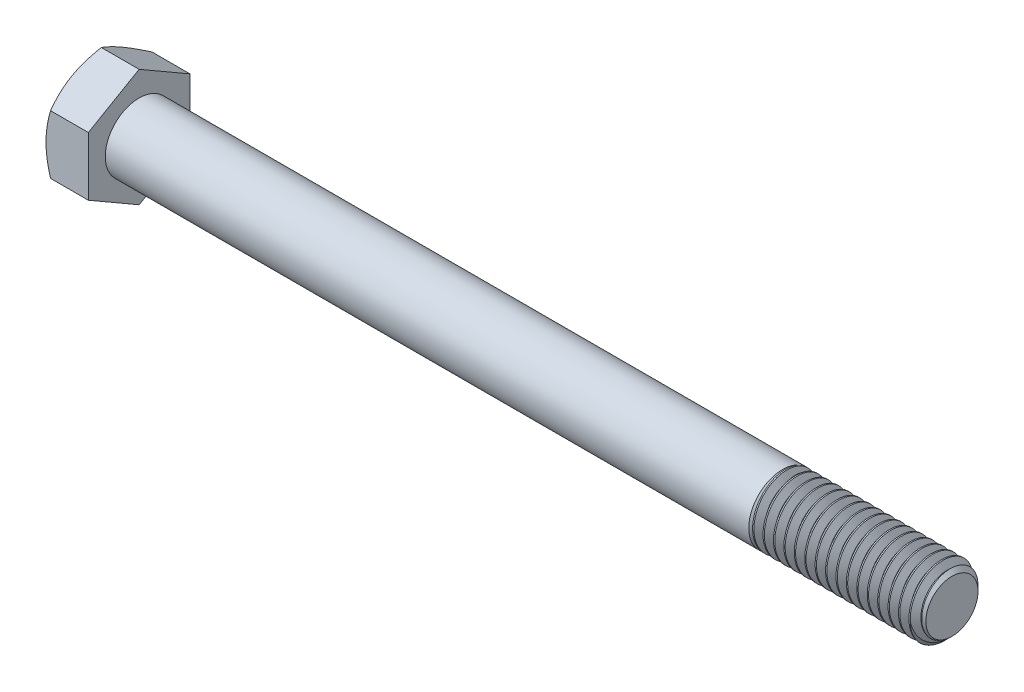
SolidWorks part; units mm, degrees
material "Plain Carbon Steel"
ref_plane "Front Plane" through (0, 0, 0) normal (0, 0, 1) x (1, 0, 0)
ref_plane "Top Plane" through (0, 0, 0) normal (0, 1, 0) x (1, 0, 0)
ref_plane "Right Plane" through (0, 0, 0) normal (1, 0, 0) x (0, 0, -1)
sketch "Sketch1" plane through (0, 0, 0) normal (0, 0, 1) x (1, 0, 0)
  line L0 (-80.1688, 0) -> (80.1688, 0) construction
  line L1 (80.1688, 6.35) -> (80.1688, -6.35) construction
  line L2 (-72.2313, 9.525) -> (-72.2313, -9.525) construction
  line L3 (-80.1688, 9.525) -> (-80.1688, -9.525) construction
  point P9 (-72.2313, 0)
  point P10 (73.3303, -6.35)
  dimension "Screw Dia" = 12.7
  dimension "Hex" = 19.05
  dimension "Head Ht" = 7.9375
  dimension "Screw Lenght" = 152.4
  dimension "D1" = 6.8385
ref_plane "Plane2" through (80.1688, 0, 0) normal (1, 0, 0) x (0, 0, -1)
sketch "Sketch5" plane through (80.1688, 0, 0) normal (1, 0, 0) x (0, 0, -1)
  circle A0 centre (0, 0) radius 6.35
extrude "Boss-Extrude3" add sketch "Sketch5" against normal up to vertex (152.4 mm away) up to point (-72.2313, 0, 0)
sketch "Sketch9" plane through (80.1688, 0, 0) normal (1, 0, 0) x (0, 0, -1)
  circle A1 centre (0, 0) radius 6.35
  circle A2 centre (0, 0) radius 6.35
  dimension "D1" = 0
curve "Helix/Spiral1" pitch 1.9538 height 33.7038 turns 17.25 parameters "Pitch"=1.9538
chamfer "Chamfer1" distance 1.4654 angle 45 1 edges at (80.1688, 0, -6.35)
sketch "Sketch10" plane through (0, 0, 0) normal (0, 0, 1) x (1, 0, 0)
  line L0 (80.1688, 6.35) -> (80.9014, 5.0809)
  line L1 (80.9014, 5.0809) -> (81.1457, 5.0809)
  line L2 (81.1457, 5.0809) -> (81.8784, 6.35)
  line L3 (80.1688, 6.35) -> (81.8784, 6.35)
  line L4 (81.0236, 6.35) -> (81.0236, 5.0809) construction
  line L5 (80.5351, 5.7155) -> (81.512, 5.7155) construction
  dimension "D1" = 60
  dimension "D2" = 0.2442
  dimension "D3" = 0.9769
sweep "Cut-Sweep1" cut profiles "Sketch10" path "Helix/Spiral1" align with end faces yes
sketch "Sketch11" plane through (0, 0, 0) normal (0, 0, 1) x (1, 0, 0)
  line L0 (-72.2313, 6.35) -> (-72.2313, 0)
  line L1 (-72.2313, 0) -> (54.7688, 0)
  line L3 (54.7688, 0) -> (48.4188, 6.35)
  line L4 (-72.2313, 6.35) -> (48.4188, 6.35)
  dimension "D1" = 45
  dimension "MIn Thread" = 31.75
revolve "Revolve1" add sketch "Sketch11" angle 360 about L1
sketch "Sketch6" plane through (-72.2312, 0, 0) normal (-1, 0, 0) x (0, 0, 1)
  line L0 (0, 9.525) -> (0, -9.525) construction
  line L1 (9.525, 5.4993) -> (0, 10.9985)
  line L2 (0, 10.9985) -> (-9.525, 5.4993)
  line L3 (-9.525, 5.4993) -> (-9.525, -5.4993)
  line L4 (-9.525, -5.4993) -> (0, -10.9985)
  line L5 (0, -10.9985) -> (9.525, -5.4993)
  line L6 (9.525, -5.4993) -> (9.525, 5.4993)
  circle A0 centre (0, 0) radius 9.525 construction
extrude "Boss-Extrude4" add sketch "Sketch6" along normal up to vertex
sketch "Sketch7" plane through (-80.1688, 0, 0) normal (-1, 0, 0) x (0, 0, 1)
  circle A0 centre (0, 0) radius 9.525 construction
  circle A1 centre (0, 0) radius 9.525
sketch "Sketch8" plane through (-80.1688, 0, 0) normal (-1, 0, 0) x (0, 0, 1)
  circle A0 centre (0, 0) radius 9.525 construction
  circle A1 centre (0, 0) radius 9.525
extrude "Cut-Extrude3" cut sketch "Sketch8" against normal through all draft 60 flip side to cut
sketch "Sketch12" plane through (-80.1688, 0, 0) normal (-1, 0, 0) x (0, 0, 1)
  line L0 (0, 7.3343) -> (0, 4.0958) construction
  line L1 (0.2858, 7.3343) -> (0.2858, 4.0958)
  line L2 (-0.2858, 7.3343) -> (-0.2857, 4.0958)
  line L3 (0, 6.35) -> (0, -6.35) construction
  arc A0 (0.2858, 7.3343) -> (-0.2858, 7.3343) centre (0, 7.3343) ccw
  arc A1 (-0.2857, 4.0958) -> (0.2858, 4.0958) centre (0, 4.0958) ccw
  circle A3 centre (0, 0) radius 3.81 construction
  circle A4 centre (0, 0) radius 7.62 construction
  point P2 (0, 5.715)
  dimension "D1" = 7.62
  dimension "D3" = 15.24
  dimension "D2" = 0.5715
extrude "Cut-Extrude4" cut sketch "Sketch12" against normal blind 0.254
pattern_circular "CirPattern1" count 3 over 360 about axis through (0, 0, 0) along (1, 0, 0) of "Cut-Extrude4"
equation "\"D2@Sketch10\" = \"Pitch@Helix/Spiral1\"*.125"
equation "\"D3@Sketch10\" = \"Pitch@Helix/Spiral1\"*.5"
equation "\"D3@Helix/Spiral1\" = \"MIn Thread@Sketch11\"+\"Pitch@Helix/Spiral1\""
equation "\"D1@Chamfer1\" = \"Pitch@Helix/Spiral1\"*.75"
equation "\"D1@Sketch12\" = \"Hex@Sketch1\"*.4"
equation "\"D3@Sketch12\" = \"Hex@Sketch1\"*.8"
equation "\"D2@Sketch12\" = \"Hex@Sketch1\"*.03"
equation "\"D1@Sketch1\" = \"Pitch@Helix/Spiral1\"*3.5"
